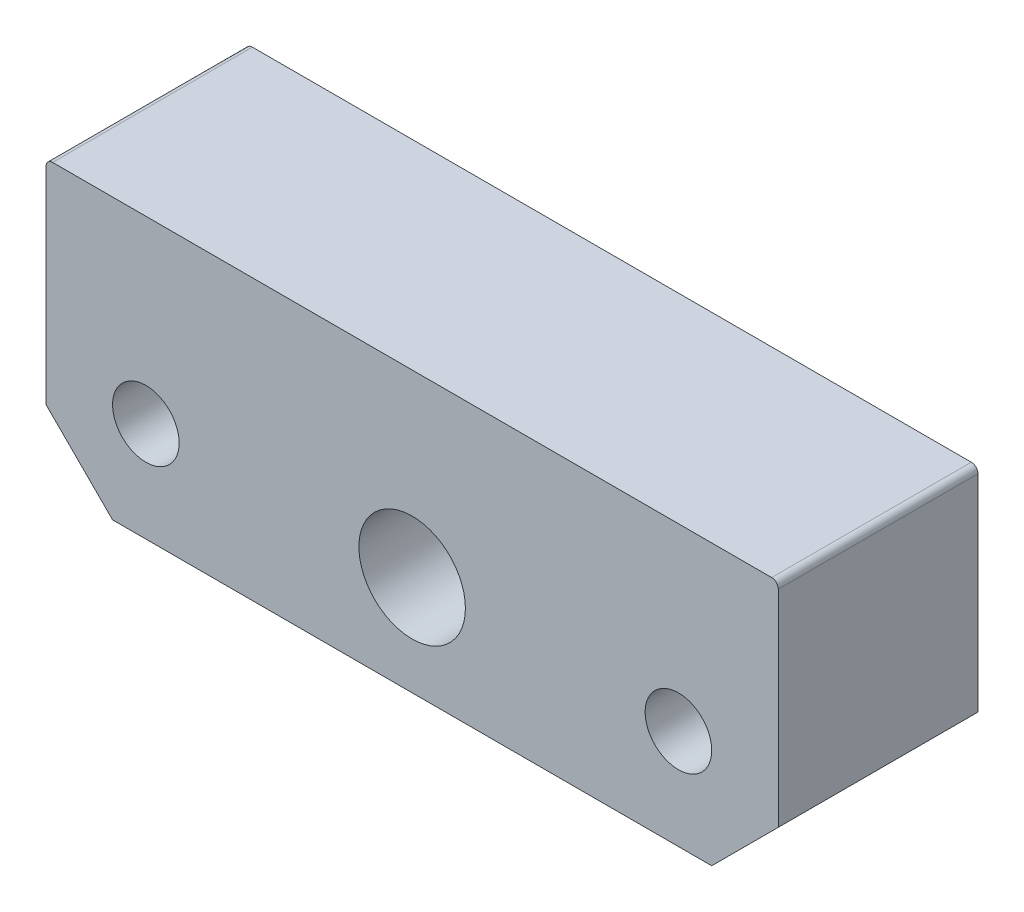
SolidWorks part; units mm, degrees
ref_plane "Alzado" through (0, 0, 0) normal (0, 0, 1) x (1, 0, 0)
ref_plane "Planta" through (0, 0, 0) normal (0, 1, 0) x (1, 0, 0)
ref_plane "Vista lateral" through (0, 0, 0) normal (1, 0, 0) x (0, 0, -1)
sketch "Croquis1" plane through (0, 0, 0) normal (0, 0, 1) x (1, 0, 0)
  line L1 (-55, -21) -> (55, -21)
  line L2 (-55, -21) -> (-55, 21)
  line L3 (-55, 21) -> (55, 21)
  line L4 (55, -21) -> (55, 21)
  line L5 (-55, -21) -> (55, 21) construction
  line L6 (-55, 21) -> (55, -21) construction
  point P0 (0, 0)
  dimension "D1" = 42
  dimension "D2" = 110
extrude "Saliente-Extruir1" add sketch "Croquis1" along normal blind 30
chamfer "Chaflán1" distance 10 angle 45 2 edges at (-55, -21, 15) (55, -21, 15)
fillet "Redondeo1" radius 1 2 edges at (-55, 21, 15) (55, 21, 15)
sketch "Croquis2" plane through (0, 0, 30) normal (0, 0, 1) x (1, 0, 0)
  line L0 (-40, -6) -> (40, -6) construction
  line L1 (54, 21) -> (-54, 21) construction
  line L2 (0, 21) -> (0, -21) construction
  line L3 (-45, -21) -> (45, -21) construction
  circle A0 centre (-40, -6) radius 5
  circle A1 centre (40, -6) radius 5
  circle A2 centre (0, -6) radius 8
  point P3 (0, -6)
  point P4 (0, -6)
  dimension "D2" = 10
  dimension "D3" = 16
  dimension "D1" = 80
  dimension "D4" = 27
extrude "Cortar-Extruir1" cut sketch "Croquis2" against normal blind 30
